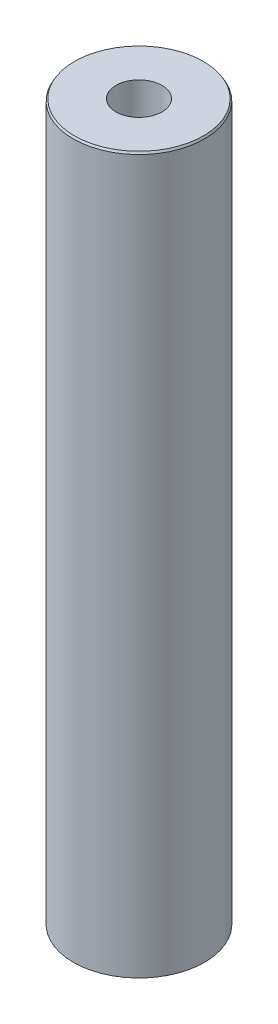
SolidWorks part; units mm, degrees
ref_plane "Front Plane" through (0, 0, 0) normal (0, 0, 1) x (1, 0, 0)
ref_plane "Top Plane" through (0, 0, 0) normal (0, 1, 0) x (1, 0, 0)
ref_plane "Right Plane" through (0, 0, 0) normal (1, 0, 0) x (0, 0, -1)
sketch "Sketch1" plane through (0, 0, 0) normal (0, 1, 0) x (1, 0, 0)
  circle A0 centre (0, 0) radius 55
  dimension "SHAFT_OD" = 110
extrude "Boss-Extrude1" add sketch "Sketch1" along normal blind 600
sketch "Sketch2" plane through (0, 0, 0) normal (0, 1, 0) x (1, 0, 0)
  circle A0 centre (0, 0) radius 19.2787
  dimension "BORE_D" = 38.5575
extrude "Cut-Extrude1" cut sketch "Sketch2" along normal through all
chamfer "Chamfer1" distance 1.7022 angle 30 2 edges at (0, 600, 55) (0, 0, 55) first distance on face at (0, 600, 55) first distance on face at (0, 0, 19.2787)
